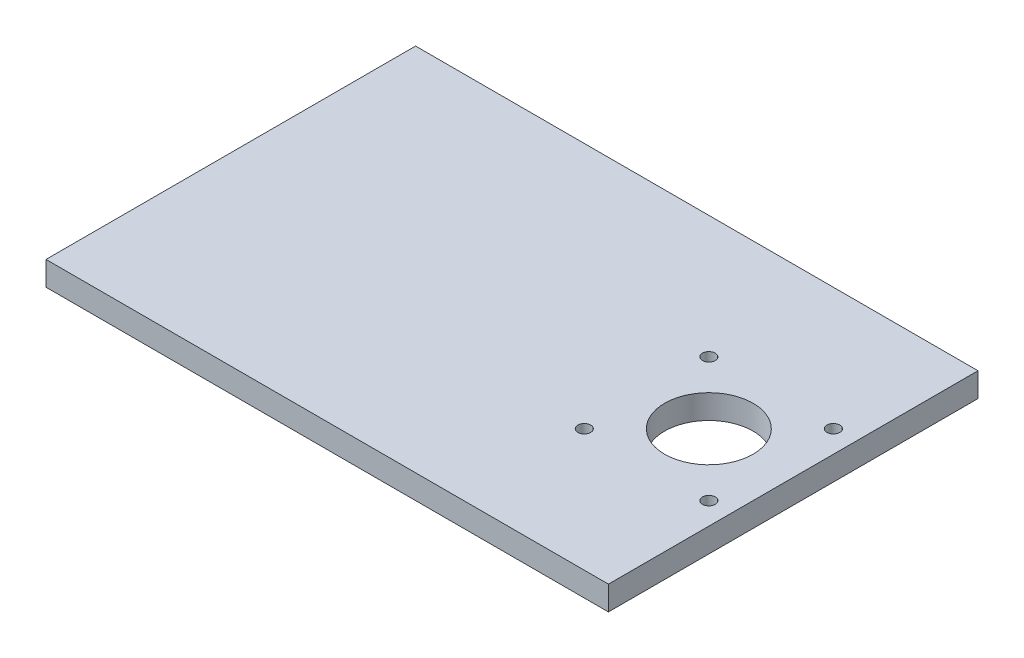
SolidWorks part; units mm, degrees
material "Maple"
ref_plane "Front Plane" through (0, 0, 0) normal (0, 0, 1) x (1, 0, 0)
ref_plane "Top Plane" through (0, 0, 0) normal (0, 1, 0) x (1, 0, 0)
ref_plane "Right Plane" through (0, 0, 0) normal (1, 0, 0) x (0, 0, -1)
sketch "Sketch1" plane through (0, 0, 0) normal (0, 1, 0) x (1, 0, 0)
  line L1 (-70, 46) -> (70, 46)
  line L2 (-70, 46) -> (-70, -46)
  line L3 (-70, -46) -> (70, -46)
  line L4 (70, 46) -> (70, -46)
  line L5 (-70, 46) -> (70, -46) construction
  line L6 (-70, -46) -> (70, 46) construction
  point P0 (0, 0)
  dimension "D1" = 140
  dimension "D2" = 92
extrude "Boss-Extrude1" add sketch "Sketch1" along normal blind 6
ref_plane "Plane1" through (0, 3, 0) normal (0, 1, 0) x (1, 0, 0)
ref_plane "Plane2" through (0, 0, 0) normal (0, 0, 1) x (1, 0, 0)
sketch "Sketch2" plane through (0, 6, 0) normal (0, 1, 0) x (1, 0, 0)
  line L0 (-70, 0) -> (70, 0) construction
  line L1 (-70, 46) -> (-70, -46) construction
  line L2 (70, -46) -> (70, 46) construction
  line L4 (40, 10) -> (70, 10)
  line L5 (40, 10) -> (40, -10)
  line L6 (40, -10) -> (70, -10)
  line L7 (70, 10) -> (70, -10)
  dimension "D1" = 30
  dimension "D2" = 20
extrude "Cut-Extrude1" [suppressed] cut sketch "Sketch2" against normal through all
sketch "Sketch3" plane through (0, 6, 0) normal (0, 1, 0) x (1, 0, 0)
  circle A0 centre (49, 0) radius 11 construction
  circle A1 centre (33.5, -15.5) radius 1.6 construction
  circle A2 centre (33.5, 15.5) radius 1.6 construction
  circle A3 centre (64.5, 15.5) radius 1.6 construction
  circle A4 centre (64.5, -15.5) radius 1.6 construction
  circle A5 centre (49, 0) radius 11
  circle A6 centre (33.5, -15.5) radius 1.6
  circle A7 centre (33.5, 15.5) radius 1.6
  circle A8 centre (64.5, 15.5) radius 1.6
  circle A9 centre (64.5, -15.5) radius 1.6
extrude "Cut-Extrude2" cut sketch "Sketch3" against normal through all
